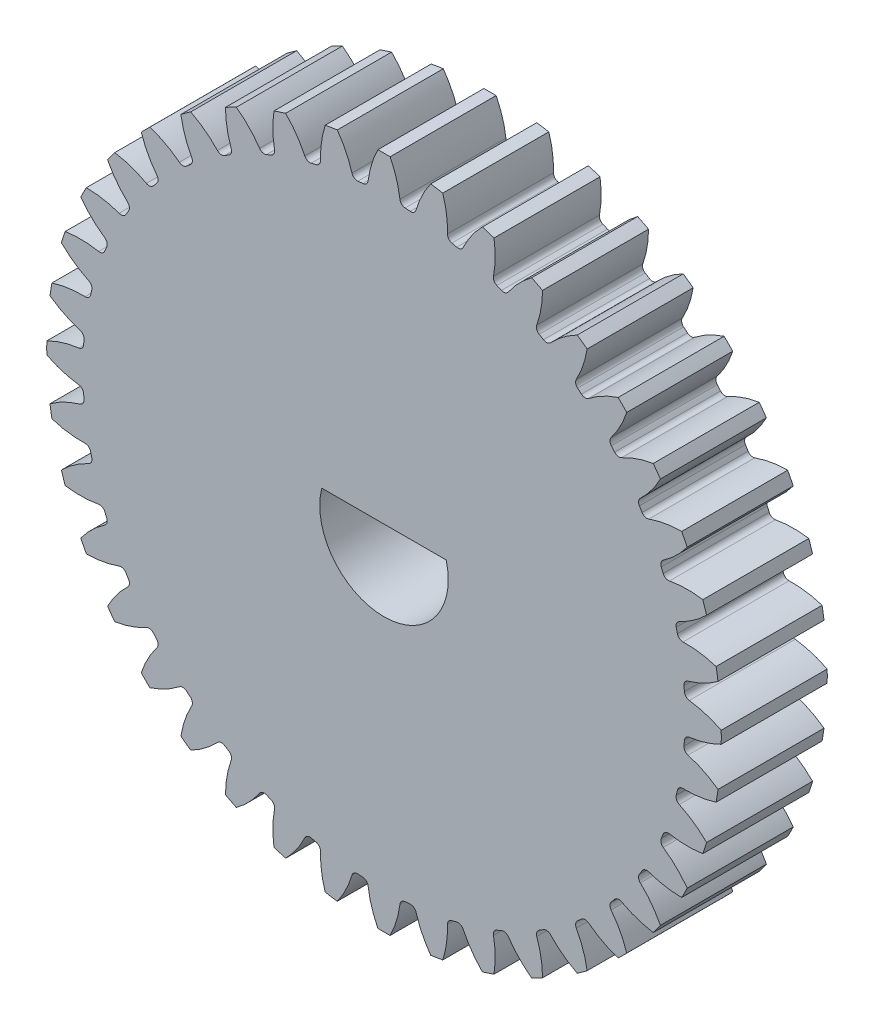
SolidWorks part; units mm, degrees
material "ABS"
ref_plane "Plane1" through (0, 0, 0) normal (0, 0, 1) x (1, 0, 0)
ref_plane "Plane2" through (0, 0, 0) normal (0, 1, 0) x (1, 0, 0)
ref_plane "Plane3" through (0, 0, 0) normal (1, 0, 0) x (0, 0, -1)
sketch "Esquisse1" plane through (0, 0, 0) normal (0, 0, 1) x (1, 0, 0)
  circle A0 centre (0, 0) radius 1.15
  dimension "D1" = 2.3
extrude "Base-Extrusion" add sketch "Esquisse1" along normal blind 2.5
sketch "Parametres" plane through (0, 0, 2.5) normal (0, 0, 1) x (1, 0, 0)
  line L0 (-33.4711, 41.7411) -> (6.5289, 41.7411)
  line L1 (-33.4711, 34.0759) -> (-32.9711, 34.0759)
  line L2 (-33.4711, 23.0892) -> (-13.4711, 23.0892)
  line L3 (-33.4711, -2.6579) -> (-33.1221, -2.6579)
  line L4 (-38.9094, -12.5583) -> (-35.7678, -12.5583)
  line L5 (-48.8826, -19.2556) -> (-38.8826, -19.2556)
  line L6 (-48.8826, -29.9283) -> (-38.3826, -29.9283)
  line L7 (-48.8826, -38.2322) -> (-39.5076, -38.2322)
  line L8 (-48.8826, -45.1309) -> (-39.4856, -45.1309)
  line L9 (-48.8826, -60.7647) -> (-48.0972, -60.7647)
  line L10 (-48.8826, -76.1039) -> (-47.8644, -76.1039)
  line L11 (-48.8826, -88.0795) -> (-48.4201, -88.0795)
  line L12 (-48.8826, -98.8973) -> (-48.5022, -98.8973)
  line L13 (16.9123, -61.9871) -> (21.4123, -61.9871)
  line L14 (18.5152, -81.0212) -> (24.7231, -81.0212)
  line L15 (18.5152, -96.0481) -> (20.5906, -96.0481)
  line L16 (-33.4711, 13.8609) -> (-26.8711, 13.8609)
sketch "Esquisse3" plane through (0, 0, 0) normal (0, 0, 1) x (1, 0, 0)
  line L0 (0, 0) -> (0, 29.3764) construction
  line L1 (-0.7356, 9.3461) -> (0, 0)
  line L2 (0, 0) -> (0.7356, 9.3461)
  line L3 (0, 0) -> (0.5088, 9.3831) construction
  line L4 (0, 0) -> (0.1902, 10.4983) construction
  line L5 (0, 0) -> (0.3926, 9.9923) construction
  arc A0 (0.1902, 10.4983) -> (0.5107, 9.3611) centre (-2.5179, 9.1213) cw
  arc A1 (-0.1902, 10.4983) -> (-0.5107, 9.3611) centre (2.5179, 9.1213) ccw
  arc A2 (0.7356, 9.3461) -> (0.5107, 9.3611) centre (0, 0) ccw
  arc A3 (-0.7356, 9.3461) -> (-0.5107, 9.3611) centre (0, 0) cw
  arc A4 (0.1902, 10.4983) -> (-0.1902, 10.4983) centre (0, 0) ccw
  dimension "D4" = 9
  dimension "D5" = 9.3969
  dimension "D6" = 10
  dimension "D1" = 10.5
  dimension "D2" = 3.104
  dimension "D3" = 2.25
  dimension "D7" = 1.038
  dimension "D8" = 9.375
extrude "Boss.-Extru.1" add sketch "Esquisse3" along normal blind 3.3
fillet "Congé1" radius 0.175 2 edges at (0.5107, 9.3611, 1.65) (-0.5107, 9.3611, 1.65)
ref_axis "Axe1" through (0, 0, 53.3) along (0, 0, -1)
pattern_circular "Répétition circulaire4" count 40 every 9 about axis through (0, 0, 53.3) along (0, 0, -1) of "Boss.-Extru.1", "Congé1"
sketch "Esquisse4" plane through (0, 0, 3.3) normal (0, 0, 1) x (1, 0, 0)
  line L0 (-1.9365, 0.5) -> (1.9365, 0.5)
  arc A0 (-1.9365, 0.5) -> (1.9365, 0.5) centre (0, 0) ccw
  dimension "D1" = 4
  dimension "D2" = 2.5
extrude "Enlèv. mat.-Extru.1" cut sketch "Esquisse4" against normal blind 10 contours L0 A0
equation "\"PI@Parametres\" = 3.141592654"
equation "\"Alpha_rad@Parametres\" = \"Alpha@Parametres\"*\"PI@Parametres\"/180"
equation "\"R@Parametres\" = \"Z@Parametres\"*\"m@Parametres\"/2"
equation "\"RT@Parametres\" = \"R@Parametres\"+\"m@Parametres\""
equation "\"RP@Parametres\" = \"R@Parametres\"-1.25*\"m@Parametres\""
equation "\"Rb@Parametres\" = \"R@Parametres\"*cos(\"Alpha_rad@Parametres\")"
equation "\"E@Parametres\" = \"PI@Parametres\"*\"R@Parametres\"/\"Z@Parametres\""
equation "\"Eb@Parametres\" = \"Rb@Parametres\"*((\"PI@Parametres\"*\"m@Parametres\"/(2*\"R@Parametres\"))+2*(tan(\"Alpha_rad@Parametres\")-\"Alpha_rad@Parametres\"))"
equation "\"As@Parametres\" = atn(sqr(\"RT@Parametres\"*\"RT@Parametres\"-\"Rb@Parametres\"*\"Rb@Parametres\")/\"Rb@Parametres\")"
equation "\"Et@Parametres\" = \"RT@Parametres\"*((\"E@Parametres\"/\"R@Parametres\")+2*(tan(\"Alpha_rad@Parametres\")-\"Alpha_rad@Parametres\"-tan(\"As@Parametres\")+\"As@Parametres\"))"
equation "\"Ap@Parametres\" = (\"E@Parametres\"/\"R@Parametres\")*180/\"PI@Parametres\""
equation "\"Ab@Parametres\" = (\"Eb@Parametres\"/\"Rb@Parametres\")*180/\"PI@Parametres\""
equation "\"At@Parametres\" = (\"Et@Parametres\"/\"RT@Parametres\")*180/\"PI@Parametres\""
equation "\"D7@Esquisse3\" = \"At@Parametres\"/2"
equation "\"D3@Esquisse3\"=\"Ap@Parametres\"/2"
equation "\"D2@Esquisse3\"=\"Ab@Parametres\"/2"
equation "\"D5@Esquisse3\"=\"Rb@Parametres\""
equation "\"D6@Esquisse3\"=\"R@Parametres\""
equation "\"D1@Esquisse3\"=\"RT@Parametres\""
equation "\"D4@Esquisse3\" = \"Ap@Parametres\"*2"
equation "\"D1@Boss.-Extru.1\" = \"k@Parametres\"*\"m@Parametres\""
equation "\"D1@Congé1\" = 0.35*\"m@Parametres\""
equation "\"D2@Répétition circulaire4\" = \"Ap@Parametres\"*2"
equation "\"D1@Répétition circulaire4\" = \"Z@Parametres\""
equation "\"D8@Esquisse3\" = \"RP@Parametres\""
